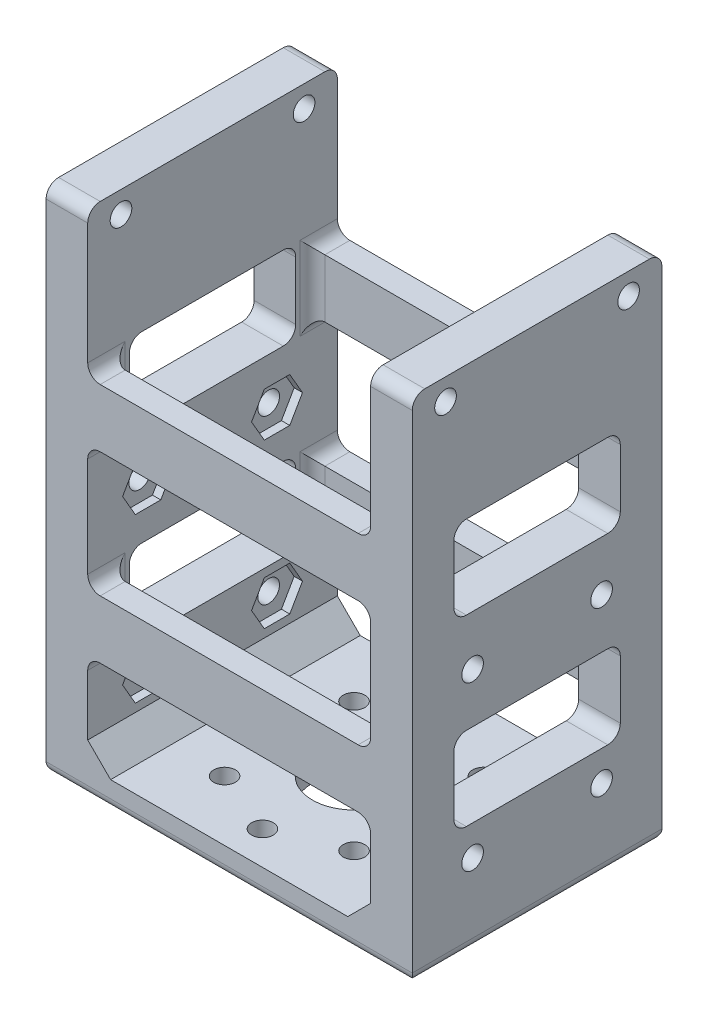
SolidWorks part; units mm, degrees
ref_plane "Front Plane" through (0, 0, 0) normal (0, 0, 1) x (1, 0, 0)
ref_plane "Top Plane" through (0, 0, 0) normal (0, 1, 0) x (1, 0, 0)
ref_plane "Right Plane" through (0, 0, 0) normal (1, 0, 0) x (0, 0, -1)
sketch "Sketch1" plane through (0, 0, 0) normal (0, 1, 0) x (1, 0, 0)
  line L1 (0, 0) -> (44, 0)
  line L2 (0, 0) -> (0, 30)
  line L3 (0, 30) -> (44, 30)
  line L4 (44, 0) -> (44, 30)
  dimension "D1" = 30
  dimension "D2" = 44
extrude "Boss-Extrude1" add sketch "Sketch1" along normal blind 54.5
sketch "Sketch5" plane through (0, 54.5, 0) normal (0, 1, 0) x (1, 0, 0)
  line L0 (0, 0) -> (44, 0) construction
  line L1 (0, 30) -> (5, 30)
  line L2 (0, 30) -> (0, 0)
  line L3 (0, 0) -> (5, 0)
  line L4 (5, 30) -> (5, 0)
  dimension "D1" = 5
ref_plane "Plane1" through (22, 0, 0) normal (-1, 0, 0) x (0, 0, 1)
extrude "Boss-Extrude3" add sketch "Sketch5" along normal blind 6.8
sketch "Sketch9" plane through (5, 0, 0) normal (1, 0, 0) x (0, 0, -1)
  line L0 (30, 61.3) -> (30, 54.5) construction
  line L2 (0, 61.3) -> (0, 54.5) construction
  line L4 (0, 61.3) -> (30, 61.3) construction
  circle A0 centre (26, 58.7) radius 1.3
  circle A1 centre (4, 58.7) radius 1.3
  dimension "D1" = 2.6
  dimension "D2" = 4
  dimension "D3" = 2.6
  dimension "D4" = 2.6
  dimension "D5" = 4
  dimension "D6" = 2.6
extrude "Cut-Extrude6" cut sketch "Sketch9" against normal through all
mirror "Mirror2" about plane through (22, 0, 0) normal (-1, 0, 0) of "Boss-Extrude3", "Cut-Extrude6"
fillet "Fillet1" radius 1.5 4 edges at (41.5, 61.3, -30) (2.5, 61.3, -30) (2.5, 61.3, 0) (41.5, 61.3, 0)
fillet "Fillet2" radius 1.25 4 edges at (0, 0, -15) (22, 0, -30) (22, 0, 0) (44, 0, -15)
sketch "Sketch11" plane through (0, 54.5, 0) normal (0, 1, 0) x (1, 0, 0)
  line L0 (39, 0) -> (39, 30) construction
  line L1 (39, 27) -> (5, 27)
  line L2 (39, 27) -> (39, 3)
  line L3 (39, 3) -> (5, 3)
  line L4 (5, 27) -> (5, 3)
  line L5 (5, 0) -> (5, 30) construction
  line L6 (39, 30) -> (5, 30) construction
  line L7 (5, 0) -> (39, 0) construction
  dimension "D1" = 3
  dimension "D2" = 3
extrude "Cut-Extrude7" cut sketch "Sketch11" against normal blind 51.25
ref_point "Point1"
sketch "Sketch13" plane through (0, 0, 0) normal (0, -1, 0) x (1, 0, 0)
  circle A0 centre (22, -15) radius 5
  circle A1 centre (33, -15) radius 1.3
  dimension "D1" = 10
  dimension "D2" = 2.6
  dimension "D3" = 11
extrude "Cut-Extrude8" cut sketch "Sketch13" against normal blind 3.5
ref_axis "Axis1" through (22, 0, -15) along (0, -1, 0)
pattern_circular "CirPattern1" count 8 over 360 about axis through (22, 0, -15) along (0, -1, 0) of "Cut-Extrude8"
ref_plane "Plane2" through (0, 0, -15) normal (0, 0, -1) x (-1, 0, 0)
sketch "Sketch15" plane through (44, 0, 0) normal (1, 0, 0) x (0, 0, -1)
  line L0 (0, 1.25) -> (30, 1.25) construction
  line L1 (25, 13.25) -> (5, 13.25)
  line L2 (25, 13.25) -> (25, 23.25)
  line L3 (25, 23.25) -> (5, 23.25)
  line L4 (5, 13.25) -> (5, 23.25)
  line L5 (30, 59.8) -> (30, 1.25) construction
  line L6 (0, 59.8) -> (0, 1.25) construction
  line L8 (25, 35.25) -> (5, 35.25)
  line L9 (25, 35.25) -> (25, 45.25)
  line L10 (25, 45.25) -> (5, 45.25)
  line L11 (5, 35.25) -> (5, 45.25)
  dimension "D1" = 12
  dimension "D2" = 10
  dimension "D3" = 5
  dimension "D4" = 5
  dimension "D5" = 12
  dimension "D6" = 10
extrude "Cut-Extrude10" cut sketch "Sketch15" against normal up to next
fillet "Fillet6" radius 1.5 8 edges at (41.5, 13.25, -5) (41.5, 35.25, -5) (41.5, 23.25, -5) (41.5, 45.25, -5) (41.5, 23.25, -25) (41.5, 45.25, -25) (41.5, 35.25, -25) (41.5, 13.25, -25)
mirror "Mirror4" about plane through (22, 0, 0) normal (-1, 0, 0) of "Cut-Extrude10", "Fillet6"
sketch "Sketch16" plane through (0, 0, 0) normal (0, 0, 1) x (1, 0, 0)
  line L0 (5, 54.5) -> (39, 54.5) construction
  line L5 (42.75, 0) -> (1.25, 0) construction
  line L6 (5, 14.75) -> (39, 14.75)
  line L7 (5, 54.5) -> (39, 54.5)
  line L8 (5, 54.5) -> (5, 43.75)
  line L9 (5, 43.75) -> (39, 43.75)
  line L10 (39, 54.5) -> (39, 43.75)
  line L15 (5, 36.75) -> (39, 36.75)
  line L16 (5, 36.75) -> (5, 21.75)
  line L17 (5, 21.75) -> (39, 21.75)
  line L18 (39, 36.75) -> (39, 21.75)
  line L20 (39, 59.8) -> (39, 54.5) construction
  line L21 (5, 59.8) -> (5, 54.5) construction
  line L22 (5, 14.75) -> (5, 3.25)
  line L23 (5, 3.25) -> (39, 3.25)
  line L24 (39, 14.75) -> (39, 3.25)
  dimension "D3" = 7
  dimension "D1" = 10.75
  dimension "D2" = 3.25
  dimension "D4" = 7
  dimension "D5" = 32.75
extrude "Cut-Extrude11" cut sketch "Sketch16" against normal up to next
mirror "Mirror5" about plane through (0, 0, -15) normal (0, 0, -1) of "Cut-Extrude11"
chamfer "Chamfer1" distance 2.75 angle 45 2 edges at (5, 3.25, -15) (39, 3.25, -15)
sketch "Sketch18" plane through (0, 0, 0) normal (-1, 0, 0) x (0, 0, 1)
  line L0 (-30, 59.8) -> (-30, 1.25) construction
  line L1 (-6.5, 13.25) -> (-23.5, 13.25) construction
  line L3 (-6.5, 35.25) -> (-23.5, 35.25) construction
  circle A0 centre (-22.75, 29.25) radius 1.3
  circle A1 centre (-7.25, 29.25) radius 1.3
  circle A2 centre (-22.75, 9.625) radius 1.3
  circle A3 centre (-7.25, 9.625) radius 1.3
  dimension "D1" = 2.6
  dimension "D2" = 2.6
  dimension "D10" = 2.6
  dimension "D11" = 2.6
  dimension "D3" = 15.5
  dimension "D4" = 7.25
  dimension "D5" = 6
  dimension "D6" = 6
  dimension "D7" = 15.5
  dimension "D8" = 3.625
  dimension "D9" = 3.625
  dimension "D12" = 7.25
extrude "Cut-Extrude12" cut sketch "Sketch18" against normal blind 5
fillet "Fillet7" radius 1.5 24 edges at (39, 36.75, -28.5) (39, 36.75, -1.5) (39, 14.75, -1.5) (39, 14.75, -28.5) (5, 14.75, -1.5) (5, 36.75, -1.5) (5, 36.75, -28.5) (5, 14.75, -28.5) (5, 18.25, -3) (39, 18.25, -3) (39, 40.25, -3) (5, 40.25, -3) (5, 18.25, -27) (5, 40.25, -27) (39, 40.25, -27) (39, 18.25, -27) (39, 21.75, -28.5) (5, 21.75, -1.5) (5, 21.75, -28.5) (39, 21.75, -1.5) (39, 43.75, -1.5) (39, 43.75, -28.5) (5, 43.75, -28.5) (5, 43.75, -1.5)
sketch "Sketch19" plane through (5, 0, 0) normal (1, 0, 0) x (0, 0, -1)
  line L0 (0, 6) -> (30, 6) construction
  line L1 (8.78, 26.6) -> (10.31, 29.25)
  line L2 (10.31, 29.25) -> (8.78, 31.9)
  line L3 (8.78, 31.9) -> (5.72, 31.9)
  line L4 (5.72, 31.9) -> (4.19, 29.25)
  line L5 (4.19, 29.25) -> (5.72, 26.6)
  line L6 (5.72, 26.6) -> (8.78, 26.6)
  line L7 (21.22, 26.6) -> (24.28, 26.6)
  line L8 (24.28, 26.6) -> (25.81, 29.25)
  line L9 (25.81, 29.25) -> (24.28, 31.9)
  line L10 (24.28, 31.9) -> (21.22, 31.9)
  line L11 (21.22, 31.9) -> (19.69, 29.25)
  line L12 (19.69, 29.25) -> (21.22, 26.6)
  line L13 (5.72, 6.975) -> (8.78, 6.975)
  line L14 (8.78, 6.975) -> (10.31, 9.625)
  line L15 (10.31, 9.625) -> (8.78, 12.275)
  line L16 (8.78, 12.275) -> (5.72, 12.275)
  line L17 (5.72, 12.275) -> (4.19, 9.625)
  line L18 (4.19, 9.625) -> (5.72, 6.975)
  line L19 (21.22, 6.975) -> (24.28, 6.975)
  line L20 (24.28, 6.975) -> (25.81, 9.625)
  line L21 (25.81, 9.625) -> (24.28, 12.275)
  line L22 (24.28, 12.275) -> (21.22, 12.275)
  line L23 (21.22, 12.275) -> (19.69, 9.625)
  line L24 (19.69, 9.625) -> (21.22, 6.975)
  circle A0 centre (7.25, 29.25) radius 2.65 construction
  circle A1 centre (22.75, 29.25) radius 2.65 construction
  circle A2 centre (7.25, 9.625) radius 2.65 construction
  circle A3 centre (22.75, 9.625) radius 2.65 construction
extrude "Cut-Extrude13" cut sketch "Sketch19" against normal blind 1
mirror "Mirror6" about plane through (22, 0, 0) normal (-1, 0, 0) of "Cut-Extrude13", "Cut-Extrude12"
equation "\"D4@Sketch18\"=(30-\"D3@Sketch18\")/2"
equation "\"D8@Sketch18\"=7.25/2"
equation "\"D9@Sketch18\"=7.25/2"
equation "\"WEBBING_THICK\" = 7"
equation "\"D3@Sketch16\"=\"WEBBING_THICK\""
equation "\"D1@Sketch16\"=14.25-\"WEBBING_THICK\"/2"
equation "\"D4@Sketch16\"=\"WEBBING_THICK\""
equation "\"D5@Sketch16\"=36.25-\"WEBBING_THICK\"/2"
